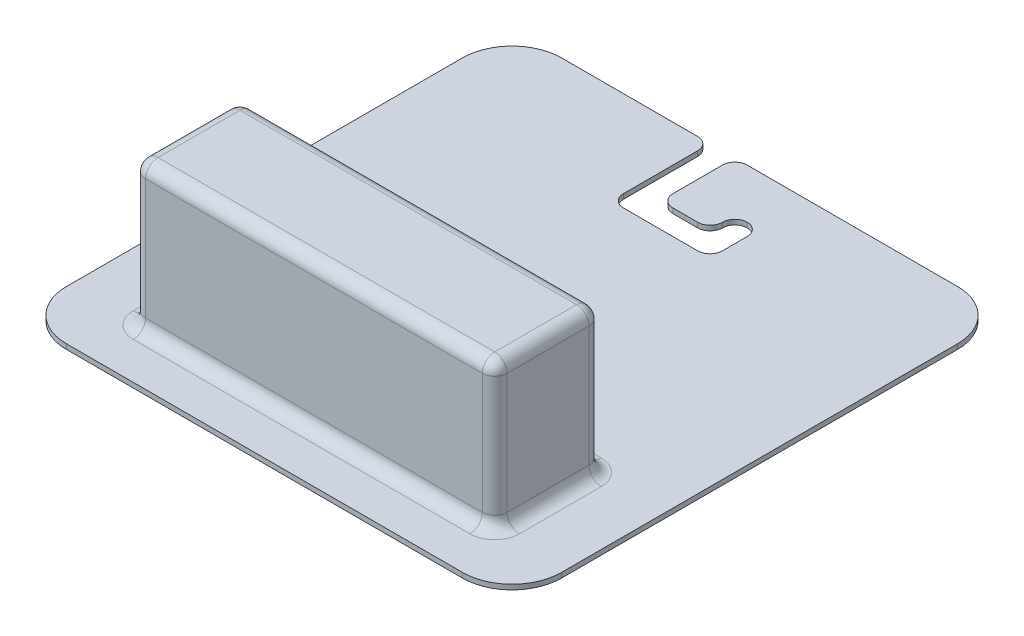
SolidWorks part; units mm, degrees
ref_plane "Front Plane" through (0, 0, 0) normal (0, 0, 1) x (1, 0, 0)
ref_plane "Top Plane" through (0, 0, 0) normal (0, 1, 0) x (1, 0, 0)
ref_plane "Right Plane" through (0, 0, 0) normal (1, 0, 0) x (0, 0, -1)
sketch "Sketch2" plane through (0, 0, 0) normal (0, 1, 0) x (1, 0, 0)
  line L1 (0, 0) -> (100, 0)
  line L2 (0, 0) -> (0, 100)
  line L3 (0, 100) -> (100, 100)
  line L4 (100, 0) -> (100, 100)
  dimension "D1" = 100
  dimension "D2" = 100
extrude "Boss-Extrude1" add sketch "Sketch2" along normal blind 1
fillet "Fillet1" radius 10 4 edges at (0, 0.5, -100) (100, 0.5, -100) (100, 0.5, 0) (0, 0.5, 0)
sketch "Sketch3" plane through (0, 1, 0) normal (0, 1, 0) x (1, 0, 0)
  line L9 (50, -900) -> (50, 49100) construction
  line L10 (10, 0) -> (90, 0) construction
  line L12 (90, 100) -> (10, 100) construction
  line L13 (40, 100) -> (40, 80)
  line L14 (40, 80) -> (60, 80)
  line L15 (60, 80) -> (60, 90)
  line L16 (60, 90) -> (55, 90)
  line L17 (55, 90) -> (55, 85)
  line L18 (55, 85) -> (45, 85)
  line L19 (45, 85) -> (45, 100)
  point P5 (50, 100)
  point P7 (50, 80)
  point P15 (50, 0)
  dimension "D1" = 5
  dimension "D2" = 5
  dimension "D3" = 20
  dimension "D4" = 20
  dimension "D5" = 5
  dimension "D6" = 10
extrude "Cut-Extrude1" cut sketch "Sketch3" against normal through all and the other way through all
fillet "Fillet2" radius 2.5 8 edges at (45, 0.5, -100) (40, 0.5, -100) (60, 0.5, -80) (60, 0.5, -90) (55, 0.5, -90) (55, 0.5, -85) (45, 0.5, -85) (40, 0.5, -80)
sketch "Sketch4" plane through (0, 1, 0) normal (0, 1, 0) x (1, 0, 0)
  line L0 (10, 0) -> (90, 0) construction
  line L1 (13.5, 10) -> (86.5, 10)
  line L2 (13.5, 10) -> (13.5, 31.54)
  line L3 (13.5, 31.54) -> (86.5, 31.54)
  line L4 (86.5, 10) -> (86.5, 31.54)
  point P6 (50, 10)
  point P7 (50, 0)
  dimension "D1" = 10
  dimension "D2" = 21.54
  dimension "D3" = 73
extrude "Boss-Extrude2" add sketch "Sketch4" along normal blind 29.32
fillet "Fillet3" radius 2.5 12 edges at (50, 30.32, -10) (86.5, 30.32, -20.77) (13.5, 30.32, -20.77) (50, 30.32, -31.54) (13.5, 15.66, -10) (13.5, 15.66, -31.54) (86.5, 15.66, -10) (86.5, 15.66, -31.54) (86.5, 1, -20.77) (50, 1, -10) (13.5, 1, -20.77) (50, 1, -31.54)
sketch "Sketch5" plane through (0, 1, 0) normal (0, 1, 0) x (1, 0, 0)
  line L0 (135.0916, 77.2921) -> (665.7583, 77.2921) construction
